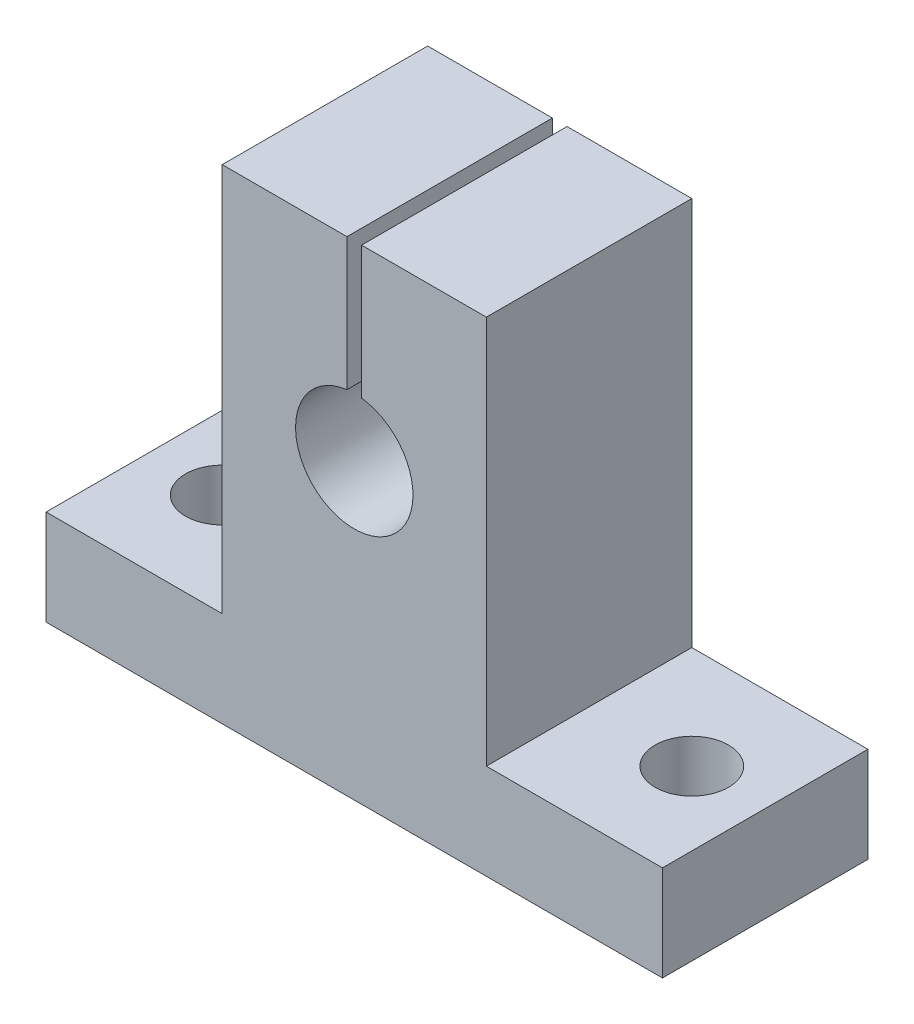
SolidWorks part; units mm, degrees
ref_plane "Front Plane" through (0, 0, 0) normal (0, 0, 1) x (1, 0, 0)
ref_plane "Top Plane" through (0, 0, 0) normal (0, 1, 0) x (1, 0, 0)
ref_plane "Right Plane" through (0, 0, 0) normal (1, 0, 0) x (0, 0, -1)
sketch "Sketch1" plane through (0, 0, 0) normal (0, 0, 1) x (1, 0, 0)
  line L0 (9, 3.25) -> (21, 3.25)
  line L1 (-21, -3.25) -> (21, -3.25)
  line L2 (-21, -3.25) -> (-21, 3.25)
  line L3 (-21, 3.25) -> (-9, 3.25)
  line L4 (21, -3.25) -> (21, 3.25)
  line L5 (-21, -3.25) -> (21, 3.25) construction
  line L6 (-21, 3.25) -> (21, -3.25) construction
  line L7 (-9, 29.75) -> (9, 29.75)
  line L8 (-9, 29.75) -> (-9, 3.25)
  line L10 (9, 29.75) -> (9, 3.25)
  line L11 (-9, 29.75) -> (9, 3.25) construction
  line L12 (-9, 3.25) -> (9, 29.75) construction
  point P0 (0, 0)
  point P6 (0, 16.5)
  point P11 (0, 0)
  dimension "D1" = 42
  dimension "D2" = 6.5
  dimension "D3" = 18
  dimension "D4" = 26.5
extrude "Boss-Extrude1" add sketch "Sketch1" along normal blind 7 and the other way blind 7
sketch "Sketch2" plane through (0, 0, 7) normal (0, 0, 1) x (1, 0, 0)
  line L0 (9, 29.75) -> (-9, 29.75) construction
  line L1 (-0.5, 20.7186) -> (-0.5, 29.75)
  line L4 (-0.5, 29.75) -> (0.5, 29.75)
  line L10 (0.5, 20.7186) -> (0.5, 29.75)
  arc A0 (-0.5, 20.7186) -> (0.5, 20.7186) centre (0, 16.75) ccw
  dimension "D2" = 8
  dimension "D1" = 13
  dimension "D3" = 1
extrude "Cut-Extrude1" cut sketch "Sketch2" against normal through all
sketch "Sketch3" plane through (0, 3.25, 0) normal (0, 1, 0) x (1, 0, 0)
  line L0 (21, 7) -> (21, -7) construction
  line L1 (21, -7) -> (9, -7) construction
  line L2 (0, -7.7) -> (0, 7.7) construction
  circle A0 centre (16, 0) radius 2.5
  circle A1 centre (-16, 0) radius 2.5
  point P4 (0, 0)
  point P6 (0, 0)
  dimension "D3" = 5
  dimension "D1" = 5
  dimension "D2" = 7
extrude "Cut-Extrude2" cut sketch "Sketch3" against normal through all
